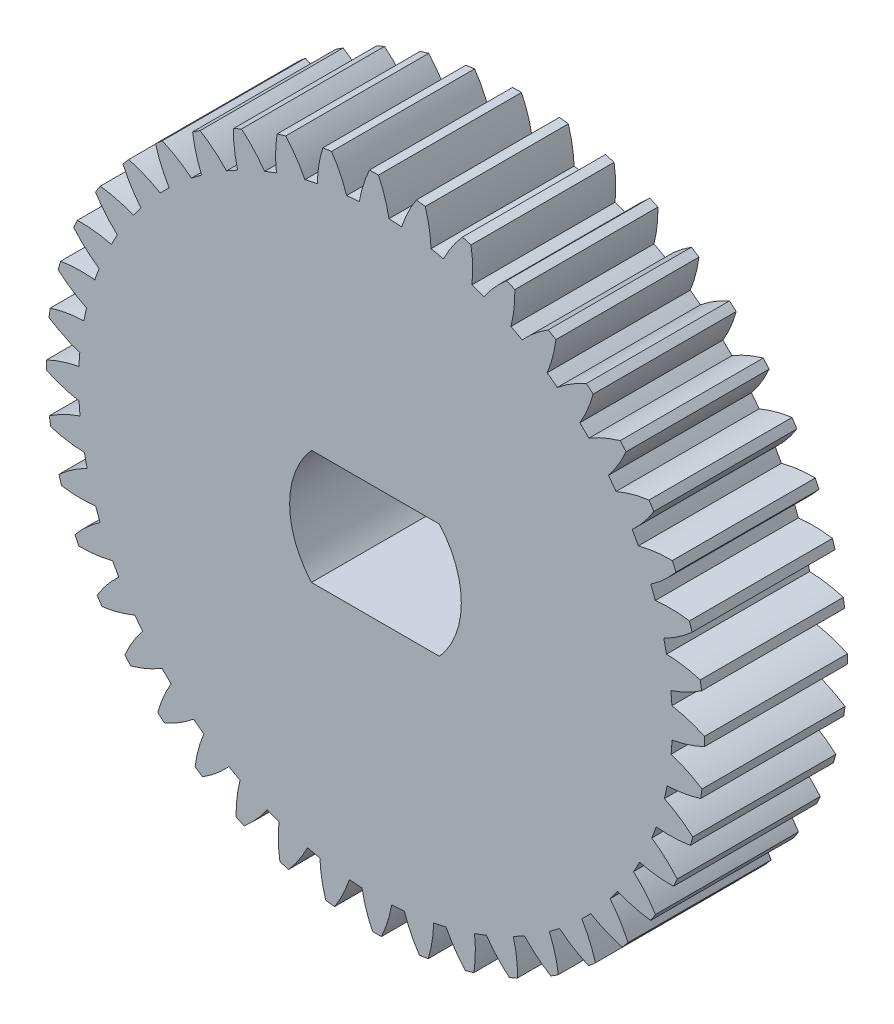
SolidWorks part; units mm, degrees
ref_plane "Front Plane" through (0, 0, 0) normal (0, 0, 1) x (1, 0, 0)
ref_plane "Top Plane" through (0, 0, 0) normal (0, 1, 0) x (1, 0, 0)
ref_plane "Right Plane" through (0, 0, 0) normal (1, 0, 0) x (0, 0, -1)
sketch "Sketch1" plane through (0, 0, 0) normal (0, 0, 1) x (1, 0, 0)
  circle A0 centre (0, 0) radius 57.1163
extrude "Boss-Extrude1" add sketch "Sketch1" along normal blind 10
extrude "Cut-Extrude5" cut sketch "Sketch6" against normal through all both and the other way through all contours A176 A703 A702 A701 A700 A699 A698 A697 A696 A695 A694 A693 A692 A691 A690 A689 A688 A687 A686 A685 A684 A683 A682 A681 A680 A679 A678 A677 A676 A675 A674 A673 A672 A671 A670 A669 A668 A667 A666 A665 A664 A663 A662 A661 A660 A659 A658 A657 A656 A655 | L0 A177 L1 A0 region at (-2.5768, 26.5219, -44.5503) region at (-125.3736, 26.5219, -44.5503)
sketch "Sketch6" plane through (-165.342, -142.9681, -44.5503) normal (0, 0, 1) x (1, 0, 0)
  line L0 (158.2931, 173.49) -> (167.2373, 173.49)
  line L1 (158.2931, 165.49) -> (167.2373, 165.49)
  arc A0 (167.2373, 165.49) -> (167.2373, 173.49) centre (162.7652, 169.49) ccw
  circle A176 centre (162.7652, 169.49) radius 126.3711
  arc A177 (158.2931, 173.49) -> (158.2931, 165.49) centre (162.7652, 169.49) ccw
  arc A528 (160.7486, 190.1407) -> (159.6974, 192.2845) centre (152.3949, 187.374) ccw
  arc A529 (159.6974, 192.2845) -> (159.0797, 192.1928) centre (162.7652, 169.49) ccw
  arc A530 (159.0797, 192.1928) -> (158.6965, 189.8361) centre (167.4937, 189.6152) ccw
  arc A531 (158.6965, 189.8361) -> (157.8302, 189.6436) centre (162.7652, 169.49) ccw
  arc A532 (157.8302, 189.6436) -> (156.4846, 191.6159) centre (149.9552, 185.7161) ccw
  arc A533 (156.4846, 191.6159) -> (155.8862, 191.4372) centre (162.7652, 169.49) ccw
  arc A534 (155.8862, 191.4372) -> (155.8423, 189.05) centre (164.5815, 190.0833) ccw
  arc A535 (155.8423, 189.05) -> (155.0123, 188.7361) centre (162.7652, 169.49) ccw
  arc A536 (155.0123, 188.7361) -> (153.3997, 190.4968) centre (147.7764, 183.7279) ccw
  arc A537 (153.3997, 190.4968) -> (152.8328, 190.2348) centre (162.7652, 169.49) ccw
  arc A538 (152.8328, 190.2348) -> (153.1291, 187.8657) centre (161.6322, 190.1321) ccw
  arc A539 (153.1291, 187.8657) -> (152.3522, 187.4368) centre (162.7652, 169.49) ccw
  arc A540 (152.3522, 187.4368) -> (150.5055, 188.9502) centre (145.9027, 181.4499) ccw
  arc A541 (150.5055, 188.9502) -> (149.9816, 188.6101) centre (162.7652, 169.49) ccw
  arc A542 (149.9816, 188.6101) -> (150.6121, 186.3073) centre (158.7061, 189.7608) ccw
  arc A543 (150.6121, 186.3073) -> (149.9041, 185.7722) centre (162.7652, 169.49) ccw
  arc A544 (149.9041, 185.7722) -> (147.8608, 187.0073) centre (144.3723, 178.9283) ccw
  arc A545 (147.8608, 187.0073) -> (147.3907, 186.5962) centre (162.7652, 169.49) ccw
  arc A546 (147.3907, 186.5962) -> (148.3424, 184.4065) centre (155.8626, 188.9768) ccw
  arc A547 (148.3424, 184.4065) -> (147.7178, 183.7762) centre (162.7652, 169.49) ccw
  arc A548 (147.7178, 183.7762) -> (145.5195, 184.7079) centre (143.2163, 176.2147) ccw
  arc A549 (145.5195, 184.7079) -> (145.1127, 184.2341) centre (162.7652, 169.49) ccw
  arc A550 (145.1127, 184.2341) -> (146.3664, 182.2021) centre (153.1596, 187.7961) ccw
  arc A551 (146.3664, 182.2021) -> (145.8378, 181.4893) centre (162.7652, 169.49) ccw
  arc A552 (145.8378, 181.4893) -> (143.5293, 182.0987) centre (142.4582, 173.3641) ccw
  arc A553 (143.5293, 182.0987) -> (143.1941, 181.5718) centre (162.7652, 169.49) ccw
  arc A554 (143.1941, 181.5718) -> (144.7242, 179.7389) centre (150.6521, 186.2427) ccw
  arc A555 (144.7242, 179.7389) -> (144.3024, 178.9581) centre (162.7652, 169.49) ccw
  arc A556 (144.3024, 178.9581) -> (141.9307, 179.2328) centre (142.1136, 170.4347) ccw
  arc A557 (141.9307, 179.2328) -> (141.6739, 178.6636) centre (162.7652, 169.49) ccw
  arc A558 (141.6739, 178.6636) -> (143.4492, 177.0671) centre (148.3912, 184.3483) ccw
  arc A559 (143.4492, 177.0671) -> (143.1429, 176.2342) centre (162.7652, 169.49) ccw
  arc A560 (143.1429, 176.2342) -> (140.7562, 176.1686) centre (142.1893, 167.4861) ccw
  arc A561 (140.7562, 176.1686) -> (140.583, 175.5686) centre (162.7652, 169.49) ccw
  arc A562 (140.583, 175.5686) -> (142.5675, 174.241) centre (146.423, 182.1515) ccw
  arc A563 (142.5675, 174.241) -> (142.3828, 173.373) centre (162.7652, 169.49) ccw
  arc A564 (142.3828, 173.373) -> (140.0298, 172.9684) centre (142.6839, 164.5782) ccw
  arc A565 (140.0298, 172.9684) -> (139.9437, 172.3498) centre (162.7652, 169.49) ccw
  arc A566 (139.9437, 172.3498) -> (142.0969, 171.3182) centre (144.7874, 179.6969) ccw
  arc A567 (142.0969, 171.3182) -> (142.0376, 170.4328) centre (162.7652, 169.49) ccw
  arc A568 (142.0376, 170.4328) -> (139.7661, 169.6974) centre (143.5874, 161.7703) ccw
  arc A569 (139.7661, 169.6974) -> (139.769, 169.0729) centre (162.7652, 169.49) ccw
  arc A570 (139.769, 169.0729) -> (142.0471, 168.3582) centre (143.5178, 177.0345) ccw
  arc A571 (142.0471, 168.3582) -> (142.1144, 167.4734) centre (162.7652, 169.49) ccw
  arc A572 (142.1144, 167.4734) -> (139.9707, 166.4222) centre (144.8812, 159.1196) ccw
  arc A573 (139.9707, 166.4222) -> (140.0624, 165.8044) centre (162.7652, 169.49) ccw
  arc A574 (140.0624, 165.8044) -> (142.419, 165.4212) centre (142.64, 174.2185) ccw
  arc A575 (142.419, 165.4212) -> (142.6116, 164.555) centre (162.7652, 169.49) ccw
  arc A576 (142.6116, 164.555) -> (140.6393, 163.2094) centre (146.5391, 156.68) ccw
  arc A577 (140.6393, 163.2094) -> (140.818, 162.611) centre (162.7652, 169.49) ccw
  arc A578 (140.818, 162.611) -> (143.2052, 162.5671) centre (142.1719, 171.3062) ccw
  arc A579 (143.2052, 162.5671) -> (143.5191, 161.7371) centre (162.7652, 169.49) ccw
  arc A580 (143.5191, 161.7371) -> (141.7584, 160.1245) centre (148.5273, 154.5012) ccw
  arc A581 (141.7584, 160.1245) -> (142.0204, 159.5576) centre (162.7652, 169.49) ccw
  arc A582 (142.0204, 159.5576) -> (144.3895, 159.8539) centre (142.123, 168.357) ccw
  arc A583 (144.3895, 159.8539) -> (144.8183, 159.077) centre (162.7652, 169.49) ccw
  arc A584 (144.8183, 159.077) -> (143.305, 157.2302) centre (150.8053, 152.6275) ccw
  arc A585 (143.305, 157.2302) -> (143.6451, 156.7064) centre (162.7652, 169.49) ccw
  arc A586 (143.6451, 156.7064) -> (145.9479, 157.3368) centre (142.4944, 165.4309) ccw
  arc A587 (145.9479, 157.3368) -> (146.4829, 156.6288) centre (162.7652, 169.49) ccw
  arc A588 (146.4829, 156.6288) -> (145.2478, 154.5856) centre (153.3268, 151.097) ccw
  arc A589 (145.2478, 154.5856) -> (145.659, 154.1154) centre (162.7652, 169.49) ccw
  arc A590 (145.659, 154.1154) -> (147.8486, 155.0672) centre (143.2784, 162.5873) ccw
  arc A591 (147.8486, 155.0672) -> (148.479, 154.4425) centre (162.7652, 169.49) ccw
  arc A592 (148.479, 154.4425) -> (147.5473, 152.2443) centre (156.0405, 149.941) ccw
  arc A593 (147.5473, 152.2443) -> (148.0211, 151.8375) centre (162.7652, 169.49) ccw
  arc A594 (148.0211, 151.8375) -> (150.0531, 153.0911) centre (144.4591, 159.8843) ccw
  arc A595 (150.0531, 153.0911) -> (150.7659, 152.5626) centre (162.7652, 169.49) ccw
  arc A596 (150.7659, 152.5626) -> (150.1565, 150.2541) centre (158.8911, 149.183) ccw
  arc A597 (150.1565, 150.2541) -> (150.6834, 149.9188) centre (162.7652, 169.49) ccw
  arc A598 (150.6834, 149.9188) -> (152.5162, 151.4489) centre (146.0124, 157.3769) ccw
  arc A599 (152.5162, 151.4489) -> (153.297, 151.0272) centre (162.7652, 169.49) ccw
  arc A600 (153.297, 151.0272) -> (153.0224, 148.6555) centre (161.8205, 148.8383) ccw
  arc A601 (153.0224, 148.6555) -> (153.5916, 148.3986) centre (162.7652, 169.49) ccw
  arc A602 (153.5916, 148.3986) -> (155.1881, 150.174) centre (147.9068, 155.116) ccw
  arc A603 (155.1881, 150.174) -> (156.0209, 149.8676) centre (162.7652, 169.49) ccw
  arc A604 (156.0209, 149.8676) -> (156.0866, 147.481) centre (164.7691, 148.9141) ccw
  arc A605 (156.0866, 147.481) -> (156.6866, 147.3078) centre (162.7652, 169.49) ccw
  arc A606 (156.6866, 147.3078) -> (158.0142, 149.2922) centre (150.1037, 153.1477) ccw
  arc A607 (158.0142, 149.2922) -> (158.8821, 149.1076) centre (162.7652, 169.49) ccw
  arc A608 (158.8821, 149.1076) -> (159.2868, 146.7545) centre (167.677, 149.4087) ccw
  arc A609 (159.2868, 146.7545) -> (159.9053, 146.6685) centre (162.7652, 169.49) ccw
  arc A610 (159.9053, 146.6685) -> (160.937, 148.8217) centre (152.5583, 151.5121) ccw
  arc A611 (160.937, 148.8217) -> (161.8224, 148.7624) centre (162.7652, 169.49) ccw
  arc A612 (161.8224, 148.7624) -> (162.5578, 146.4909) centre (170.4849, 150.3121) ccw
  arc A613 (162.5578, 146.4909) -> (163.1823, 146.4938) centre (162.7652, 169.49) ccw
  arc A614 (163.1823, 146.4938) -> (163.897, 148.7719) centre (155.2207, 150.2425) ccw
  arc A615 (163.897, 148.7719) -> (164.7818, 148.8392) centre (162.7652, 169.49) ccw
  arc A616 (164.7818, 148.8392) -> (165.833, 146.6955) centre (173.1356, 151.6059) ccw
  arc A617 (165.833, 146.6955) -> (166.4508, 146.7872) centre (162.7652, 169.49) ccw
  arc A618 (166.4508, 146.7872) -> (166.8339, 149.1438) centre (158.0367, 149.3648) ccw
  arc A619 (166.8339, 149.1438) -> (167.7002, 149.3364) centre (162.7652, 169.49) ccw
  arc A620 (167.7002, 149.3364) -> (169.0458, 147.3641) centre (175.5752, 153.2638) ccw
  arc A621 (169.0458, 147.3641) -> (169.6442, 147.5428) centre (162.7652, 169.49) ccw
  arc A622 (169.6442, 147.5428) -> (169.6881, 149.9299) centre (160.949, 148.8967) ccw
  arc A623 (169.6881, 149.9299) -> (170.5181, 150.2438) centre (162.7652, 169.49) ccw
  arc A624 (170.5181, 150.2438) -> (172.1307, 148.4831) centre (177.754, 155.252) ccw
  arc A625 (172.1307, 148.4831) -> (172.6976, 148.7451) centre (162.7652, 169.49) ccw
  arc A626 (172.6976, 148.7451) -> (172.4013, 151.1143) centre (163.8982, 148.8478) ccw
  arc A627 (172.4013, 151.1143) -> (173.1782, 151.5431) centre (162.7652, 169.49) ccw
  arc A628 (173.1782, 151.5431) -> (175.0249, 150.0298) centre (179.6277, 157.5301) ccw
  arc A629 (175.0249, 150.0298) -> (175.5488, 150.3698) centre (162.7652, 169.49) ccw
  arc A630 (175.5488, 150.3698) -> (174.9184, 152.6727) centre (166.8243, 149.2192) ccw
  arc A631 (174.9184, 152.6727) -> (175.6263, 153.2077) centre (162.7652, 169.49) ccw
  arc A632 (175.6263, 153.2077) -> (177.6696, 151.9726) centre (181.1581, 160.0516) ccw
  arc A633 (177.6696, 151.9726) -> (178.1397, 152.3837) centre (162.7652, 169.49) ccw
  arc A634 (178.1397, 152.3837) -> (177.188, 154.5734) centre (169.6679, 150.0032) ccw
  arc A635 (177.188, 154.5734) -> (177.8126, 155.2038) centre (162.7652, 169.49) ccw
  arc A636 (177.8126, 155.2038) -> (180.0109, 154.272) centre (182.3142, 162.7653) ccw
  arc A637 (180.0109, 154.272) -> (180.4177, 154.7459) centre (162.7652, 169.49) ccw
  arc A638 (180.4177, 154.7459) -> (179.1641, 156.7778) centre (172.3709, 151.1838) ccw
  arc A639 (179.1641, 156.7778) -> (179.6926, 157.4906) centre (162.7652, 169.49) ccw
  arc A640 (179.6926, 157.4906) -> (182.0011, 156.8812) centre (183.0722, 165.6158) ccw
  arc A641 (182.0011, 156.8812) -> (182.3364, 157.4082) centre (162.7652, 169.49) ccw
  arc A642 (182.3364, 157.4082) -> (180.8063, 159.241) centre (174.8783, 152.7372) ccw
  arc A643 (180.8063, 159.241) -> (181.228, 160.0218) centre (162.7652, 169.49) ccw
  arc A644 (181.228, 160.0218) -> (183.5997, 159.7471) centre (183.4169, 168.5452) ccw
  arc A645 (183.5997, 159.7471) -> (183.8566, 160.3164) centre (162.7652, 169.49) ccw
  arc A646 (183.8566, 160.3164) -> (182.0812, 161.9128) centre (177.1392, 154.6316) ccw
  arc A647 (182.0812, 161.9128) -> (182.3875, 162.7457) centre (162.7652, 169.49) ccw
  arc A648 (182.3875, 162.7457) -> (184.7742, 162.8114) centre (183.3411, 171.4939) ccw
  arc A649 (184.7742, 162.8114) -> (184.9474, 163.4114) centre (162.7652, 169.49) ccw
  arc A650 (184.9474, 163.4114) -> (182.9629, 164.7389) centre (179.1075, 156.8285) ccw
  arc A651 (182.9629, 164.7389) -> (183.1476, 165.6069) centre (162.7652, 169.49) ccw
  arc A652 (183.1476, 165.6069) -> (185.5007, 166.0116) centre (182.8465, 174.4017) ccw
  arc A653 (185.5007, 166.0116) -> (185.5867, 166.6301) centre (162.7652, 169.49) ccw
  arc A654 (185.5867, 166.6301) -> (183.4335, 167.6617) centre (180.743, 159.2831) ccw
  arc A655 (183.4335, 167.6617) -> (183.4928, 168.5471) centre (162.7652, 169.49) ccw
  arc A656 (183.4928, 168.5471) -> (185.7643, 169.2825) centre (181.9431, 177.2096) ccw
  arc A657 (185.7643, 169.2825) -> (185.7614, 169.9071) centre (162.7652, 169.49) ccw
  arc A658 (185.7614, 169.9071) -> (183.4833, 170.6217) centre (182.0126, 161.9455) ccw
  arc A659 (183.4833, 170.6217) -> (183.416, 171.5066) centre (162.7652, 169.49) ccw
  arc A660 (183.416, 171.5066) -> (185.5597, 172.5578) centre (180.6492, 179.8603) ccw
  arc A661 (185.5597, 172.5578) -> (185.468, 173.1755) centre (162.7652, 169.49) ccw
  arc A662 (185.468, 173.1755) -> (183.1114, 173.5587) centre (182.8904, 164.7615) ccw
  arc A663 (183.1114, 173.5587) -> (182.9188, 174.425) centre (162.7652, 169.49) ccw
  arc A664 (182.9188, 174.425) -> (184.8911, 175.7705) centre (178.9914, 182.2999) ccw
  arc A665 (184.8911, 175.7705) -> (184.7124, 176.3689) centre (162.7652, 169.49) ccw
  arc A666 (184.7124, 176.3689) -> (182.3252, 176.4128) centre (183.3585, 167.6737) ccw
  arc A667 (182.3252, 176.4128) -> (182.0113, 177.2429) centre (162.7652, 169.49) ccw
  arc A668 (182.0113, 177.2429) -> (183.7721, 178.8555) centre (177.0031, 184.4788) ccw
  arc A669 (183.7721, 178.8555) -> (183.51, 179.4223) centre (162.7652, 169.49) ccw
  arc A670 (183.51, 179.4223) -> (181.1409, 179.1261) centre (183.4074, 170.6229) ccw
  arc A671 (181.1409, 179.1261) -> (180.7121, 179.903) centre (162.7652, 169.49) ccw
  arc A672 (180.7121, 179.903) -> (182.2254, 181.7497) centre (174.7251, 186.3525) ccw
  arc A673 (182.2254, 181.7497) -> (181.8854, 182.2735) centre (162.7652, 169.49) ccw
  arc A674 (181.8854, 182.2735) -> (179.5825, 181.6431) centre (183.036, 173.5491) ccw
  arc A675 (179.5825, 181.6431) -> (179.0475, 182.3511) centre (162.7652, 169.49) ccw
  arc A676 (179.0475, 182.3511) -> (180.2826, 184.3944) centre (172.2036, 187.8829) ccw
  arc A677 (180.2826, 184.3944) -> (179.8715, 184.8645) centre (162.7652, 169.49) ccw
  arc A678 (179.8715, 184.8645) -> (177.6818, 183.9128) centre (182.252, 176.3926) ccw
  arc A679 (177.6818, 183.9128) -> (177.0514, 184.5374) centre (162.7652, 169.49) ccw
  arc A680 (177.0514, 184.5374) -> (177.9832, 186.7357) centre (169.4899, 189.0389) ccw
  arc A681 (177.9832, 186.7357) -> (177.5093, 187.1425) centre (162.7652, 169.49) ccw
  arc A682 (177.5093, 187.1425) -> (175.4774, 185.8888) centre (181.0713, 179.0956) ccw
  arc A683 (175.4774, 185.8888) -> (174.7645, 186.4174) centre (162.7652, 169.49) ccw
  arc A684 (174.7645, 186.4174) -> (175.3739, 188.7259) centre (166.6394, 189.797) ccw
  arc A685 (175.3739, 188.7259) -> (174.847, 189.0611) centre (162.7652, 169.49) ccw
  arc A686 (174.847, 189.0611) -> (173.0142, 187.531) centre (179.518, 181.6031) ccw
  arc A687 (173.0142, 187.531) -> (172.2334, 187.9528) centre (162.7652, 169.49) ccw
  arc A688 (172.2334, 187.9528) -> (172.508, 190.3245) centre (163.7099, 190.1416) ccw
  arc A689 (172.508, 190.3245) -> (171.9388, 190.5813) centre (162.7652, 169.49) ccw
  arc A690 (171.9388, 190.5813) -> (170.3423, 188.806) centre (177.6236, 183.864) ccw
  arc A691 (170.3423, 188.806) -> (169.5095, 189.1123) centre (162.7652, 169.49) ccw
  arc A692 (169.5095, 189.1123) -> (169.4438, 191.499) centre (160.7613, 190.0659) ccw
  arc A693 (169.4438, 191.499) -> (168.8438, 191.6722) centre (162.7652, 169.49) ccw
  arc A694 (168.8438, 191.6722) -> (167.5163, 189.6877) centre (175.4267, 185.8322) ccw
  arc A695 (167.5163, 189.6877) -> (166.6483, 189.8724) centre (162.7652, 169.49) ccw
  arc A696 (166.6483, 189.8724) -> (166.2436, 192.2254) centre (157.8534, 189.5712) ccw
  arc A697 (166.2436, 192.2254) -> (165.6251, 192.3115) centre (162.7652, 169.49) ccw
  arc A698 (165.6251, 192.3115) -> (164.5935, 190.1583) centre (172.9721, 187.4678) ccw
  arc A699 (164.5935, 190.1583) -> (163.708, 190.2175) centre (162.7652, 169.49) ccw
  arc A700 (163.708, 190.2175) -> (162.9726, 192.489) centre (155.0456, 188.6678) ccw
  arc A701 (162.9726, 192.489) -> (162.3481, 192.4862) centre (162.7652, 169.49) ccw
  arc A702 (162.3481, 192.4862) -> (161.6335, 190.2081) centre (170.3097, 188.7374) ccw
  arc A703 (161.6335, 190.2081) -> (160.7486, 190.1407) centre (162.7652, 169.49) ccw
